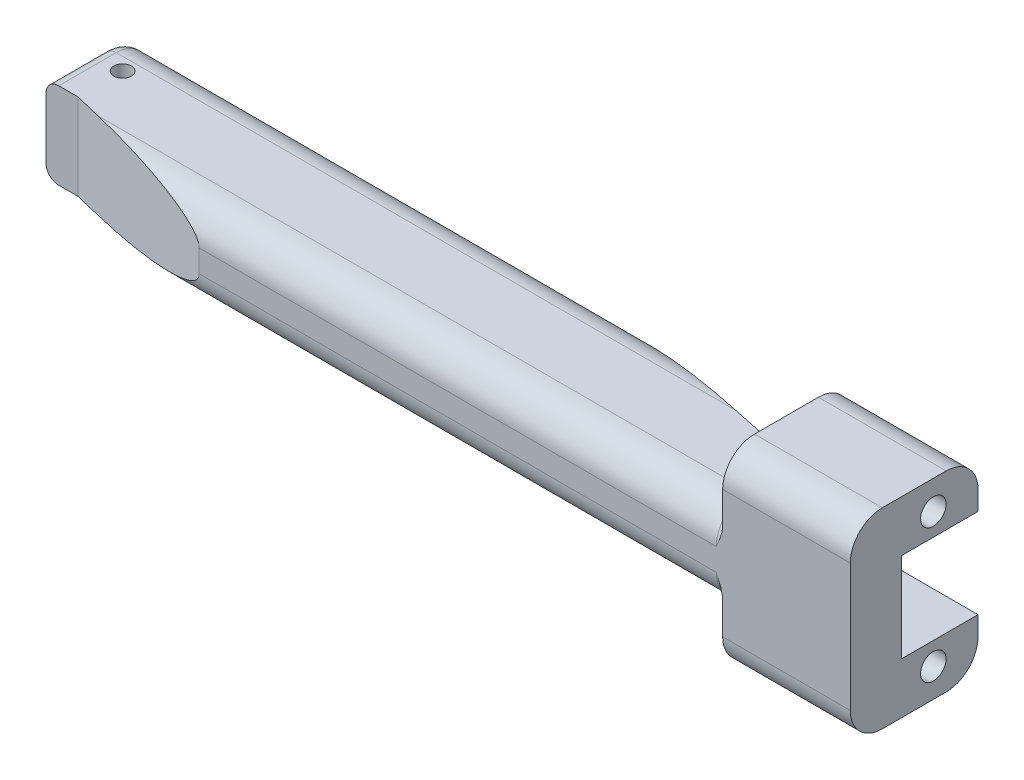
SolidWorks part; units mm, degrees
material "ABS"
ref_plane "Plan de face" through (0, 0, 0) normal (0, 0, 1) x (1, 0, 0)
ref_plane "Plan de dessus" through (0, 0, 0) normal (0, 1, 0) x (1, 0, 0)
ref_plane "Plan de droite" through (0, 0, 0) normal (1, 0, 0) x (0, 0, -1)
sketch "Esquisse1" plane through (0, 0, 0) normal (0, 0, 1) x (1, 0, 0)
  line L1 (-66, -15) -> (66, -15)
  line L2 (-66, -15) -> (-66, 15)
  line L3 (-66, 15) -> (66, 15)
  line L4 (66, -15) -> (66, 15)
  line L5 (-66, -15) -> (66, 15) construction
  line L6 (-66, 15) -> (66, -15) construction
  point P0 (0, 0)
  dimension "D1" = 132
  dimension "D2" = 30
extrude "Boss.-Extru.1" add sketch "Esquisse1" along normal blind 20
sketch "Esquisse3" plane through (0, 0, 20) normal (0, 0, 1) x (1, 0, 0)
  line L1 (-66, 15) -> (46, 15)
  line L2 (-66, 15) -> (-66, 6.75)
  line L3 (-66, 6.75) -> (46, 6.75)
  line L4 (46, 15) -> (46, 6.75)
  line L5 (-66, -15) -> (46, -15)
  line L6 (-66, -15) -> (-66, -6.75)
  line L7 (-66, -6.75) -> (46, -6.75)
  line L8 (46, -15) -> (46, -6.75)
  dimension "D1" = 13.5
  dimension "D2" = 112
extrude "Enlèv. mat.-Extru.1" cut sketch "Esquisse3" against normal through all
sketch "Esquisse4" plane through (0, -6.75, 0) normal (0, -1, 0) x (1, 0, 0)
  line L0 (-66, 0) -> (-66, 20) construction
  line L2 (-66, 0) -> (46, 0) construction
  circle A0 centre (-61, 7) radius 1.375
  dimension "D1" = 2.75
  dimension "D3" = 7
  dimension "D2" = 5
extrude "Enlèv. mat.-Extru.2" cut sketch "Esquisse4" against normal up to next
sketch "Esquisse5" plane through (46, 0, 0) normal (-1, 0, 0) x (0, 0, 1)
  line L0 (0, -6.75) -> (20, -6.75) construction
  line L1 (0, -15) -> (0, -6.75) construction
  line L3 (0, 6.75) -> (20, 6.75) construction
  circle A0 centre (7, -10.5) radius 2
  circle A1 centre (7, 10.5) radius 2
  dimension "D1" = 3.75
  dimension "D3" = 7
  dimension "D2" = 3.75
extrude "Enlèv. mat.-Extru.3" cut sketch "Esquisse5" against normal blind 80
fillet "Congé1" radius 5 4 edges at (56, -15, 20) (56, -15, 0) (56, 15, 0) (56, 15, 20)
fillet "Congé2" radius 5 4 edges at (-10, -6.75, 20) (-10, 6.75, 20) (-10, 6.75, 0) (-10, -6.75, 0)
fillet "Congé3" radius 1 6 edges at (46, 5.2855, 1.4645) (46, 5.2855, 18.5355) (46, 6.75, 10) (46, -5.2855, 1.4645) (46, -5.2855, 18.5355) (46, -6.75, 10)
sketch "Esquisse7" plane through (0, 0, 0) normal (0, 1, 0) x (1, 0, 0)
  line L0 (66, -12) -> (9.5444, 0)
  line L1 (66, -15) -> (66, -5) construction
  line L2 (46, 0) -> (66, 0) construction
  line L3 (9.5444, 0) -> (66, 0)
  line L4 (66, 0) -> (66, -12)
  dimension "D1" = 12
  dimension "D2" = 78
extrude "Enlèv. mat.-Extru.4" cut sketch "Esquisse7" against normal blind 7 and the other way blind 7
fillet "Congé4" radius 2 8 edges at (-66, -5.2855, 1.4645) (-66, 0, 0) (-66, 5.2855, 1.4645) (-66, 6.75, 10) (-66, 5.2855, 18.5355) (-66, 0, 20) (-66, -5.2855, 18.5355) (-66, -6.75, 10)
sketch "Esquisse8" plane through (0, 0, 0) normal (0, 1, 0) x (1, 0, 0)
  line L1 (-66, -15) -> (-66, -5) construction
  line L2 (45, -20) -> (-64, -20) construction
  line L3 (-36, -20) -> (-66, -20)
  line L4 (-66, -20) -> (-66, -14)
  line L5 (-66, -14) -> (-61, -14)
  line L6 (-61, -14) -> (-36, -20)
  dimension "D1" = 6
  dimension "D2" = 30
  dimension "D3" = 5
extrude "Enlèv. mat.-Extru.5" cut sketch "Esquisse8" against normal through all and the other way through all
